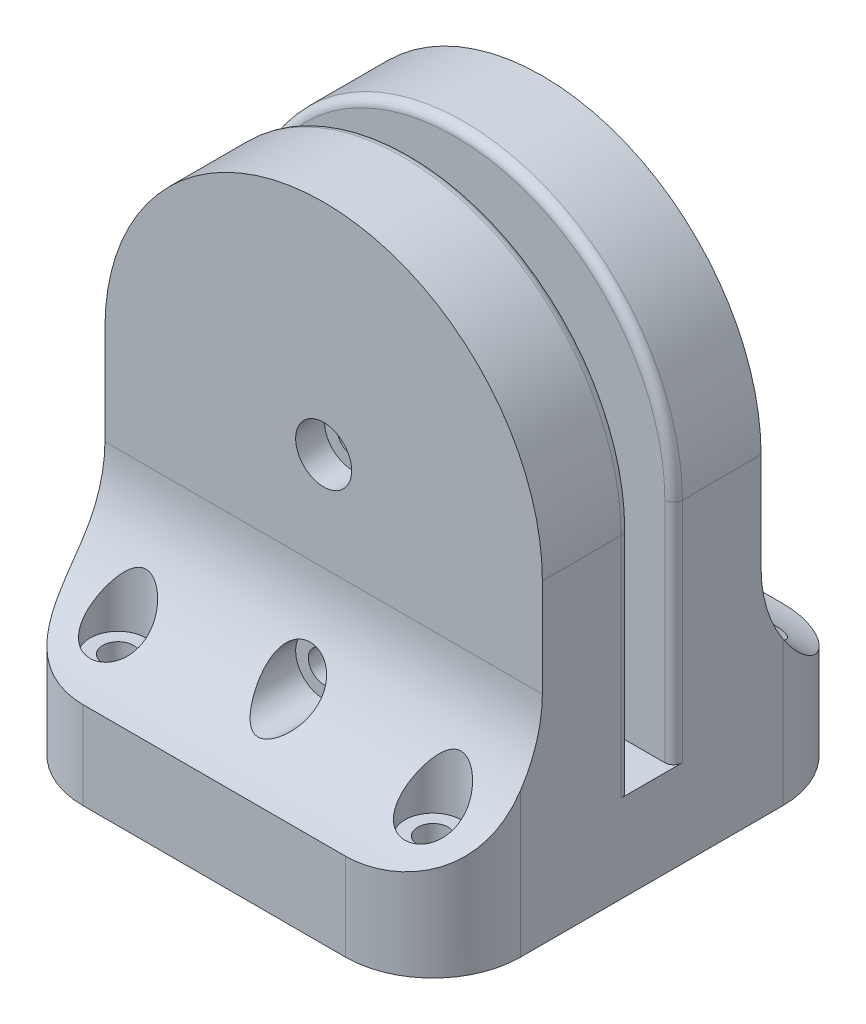
SolidWorks part; units mm, degrees
ref_plane "正面" through (0, 0, 0) normal (0, 0, 1) x (1, 0, 0)
ref_plane "平面" through (0, 0, 0) normal (0, 1, 0) x (1, 0, 0)
ref_plane "右側面" through (0, 0, 0) normal (1, 0, 0) x (0, 0, -1)
sketch "ｽｹｯﾁ1" plane through (0, 0, 0) normal (0, 1, 0) x (1, 0, 0)
  line L1 (25, 25) -> (-25, 25)
  line L2 (25, 25) -> (25, -25)
  line L3 (25, -25) -> (-25, -25)
  line L4 (-25, 25) -> (-25, -25)
  line L5 (25, 25) -> (-25, -25) construction
  line L6 (25, -25) -> (-25, 25) construction
  point P0 (0, 0)
  dimension "D1" = 50
  dimension "D2" = 50
extrude "ﾎﾞｽ - 押し出し1" add sketch "ｽｹｯﾁ1" along normal blind 10
sketch "ｽｹｯﾁ2" plane through (0, 0, 0) normal (0, 0, 1) x (1, 0, 0)
  line L0 (25, 10) -> (-25, 10)
  line L1 (-25, 10) -> (25, 10)
  line L4 (-25, 36) -> (-25, 10)
  line L5 (-25, 10) -> (25, 10)
  line L6 (-12, 10) -> (6.5, 10)
  line L7 (-25, 10) -> (25, 10)
  line L8 (25, 36) -> (25, 10)
  arc A1 (25, 36) -> (-25, 36) centre (0, 36) ccw
  circle A2 centre (0, 36) radius 1.75
  dimension "D1" = 26
  dimension "D3" = 0
  dimension "D2" = 25
  dimension "D6" = 3.5
  dimension "D4" = 26
  dimension "D5" = 26
sketch "ｽｹｯﾁ6" plane through (0, 0, 0) normal (0, 1, 0) x (1, 0, 0)
  line L0 (0, -25) -> (0, 25) construction
  line L1 (-25, -25) -> (25, -25) construction
  line L2 (25, 25) -> (-25, 25) construction
  line L3 (-25, 0) -> (25, 0) construction
  line L4 (-25, 25) -> (-25, -25) construction
  line L5 (25, -25) -> (25, 25) construction
  circle A0 centre (-18, -18) radius 1.75
  circle A1 centre (18, -18) radius 1.75
  circle A2 centre (18, 18) radius 1.75
  circle A3 centre (-18, 18) radius 1.75
  dimension "D1" = 3.5
  dimension "D2" = 18
  dimension "D3" = 18
extrude "ｶｯﾄ - 押し出し3" cut sketch "ｽｹｯﾁ6" against normal blind 5 and the other way through all
fillet "ﾌｨﾚｯﾄ1" radius 10 4 edges at (-25, 5, 25) (-25, 5, -25) (25, 5, -25) (25, 5, 25)
extrude "ﾎﾞｽ - 押し出し5" add sketch "ｽｹｯﾁ2" along normal blind 10 from offset 2.5 contours L8 A1 L4 L0 L5 A2 region at (0, 33.1466, 0)
extrude "ﾎﾞｽ - 押し出し6" add sketch "ｽｹｯﾁ2<12>" against normal blind 10 from offset 2.5 contours L8 A1 L4 L0 L5 A2 region at (0, 33.1466, 0) offset against normal yes
sketch "ｽｹｯﾁ2<12>" plane through (0, 0, 0) normal (0, 0, 1) x (1, 0, 0) same geometry as "ｽｹｯﾁ2"
sketch "ｽｹｯﾁ13" plane through (0, 0, 0) normal (0, 0, 1) x (1, 0, 0)
  circle A0 centre (0, 36) radius 21
  circle A1 centre (0, 15) radius 1.75
  point P10 (0, 36)
  dimension "D1" = 42
  dimension "D2" = 3.5
extrude "ｶｯﾄ - 押し出し4" cut sketch "ｽｹｯﾁ13" against normal through all both and the other way through all contours A1
sketch "ｽｹｯﾁ14" plane through (0, 10, 0) normal (0, 1, 0) x (1, 0, 0)
  line L0 (0, 25) -> (0, -25) construction
  line L1 (15, 25) -> (-15, 25) construction
  line L2 (-15, -25) -> (15, -25) construction
  line L3 (-25, 0) -> (25, 0) construction
  line L4 (-25, 2.5) -> (-25, -2.5) construction
  line L5 (25, -2.5) -> (25, 2.5) construction
  circle A0 centre (18, 18) radius 3.2
  circle A1 centre (18, -18) radius 3.2
  circle A2 centre (-18, -18) radius 3.2
  circle A3 centre (-18, 18) radius 3.2
  dimension "D1" = 6.4
fillet "ﾌｨﾚｯﾄ3" radius 15 2 edges at (0, 10, -12.5)
extrude "ｶｯﾄ - 押し出し6" cut sketch "ｽｹｯﾁ14" along normal through all
sketch "ｽｹｯﾁ15" plane through (0, 0, 0) normal (0, 0, 1) x (1, 0, 0)
  circle A0 centre (0, 15) radius 3.2
  dimension "D1" = 6.4
extrude "ｶｯﾄ - 押し出し7" cut sketch "ｽｹｯﾁ15" along normal through all from offset 12.5
extrude "ｶｯﾄ - 押し出し8" cut sketch "ｽｹｯﾁ15<2>" against normal through all from offset 12.5 offset against normal yes
sketch "ｽｹｯﾁ15<2>" plane through (0, 0, 0) normal (0, 0, 1) x (1, 0, 0) same geometry as "ｽｹｯﾁ15"
sketch "ｽｹｯﾁ16" plane through (0, 0, 0) normal (0, 0, 1) x (1, 0, 0)
  circle A0 centre (0, 36) radius 3.2
  dimension "D1" = 6.4
extrude "ｶｯﾄ - 押し出し9" cut sketch "ｽｹｯﾁ16" against normal blind 3.3 from offset 12.5
extrude "ｶｯﾄ - 押し出し10" cut sketch "ｽｹｯﾁ16<2>" along normal blind 3.3 from offset 12.5 offset against normal yes
sketch "ｽｹｯﾁ16<2>" plane through (0, 0, 0) normal (0, 0, 1) x (1, 0, 0) same geometry as "ｽｹｯﾁ16"
fillet "ﾌｨﾚｯﾄ5" radius 1 6 edges at (25, 23, -2.5) (-25, 23, -2.5) (0, 61, -2.5) (0, 61, 2.5)
